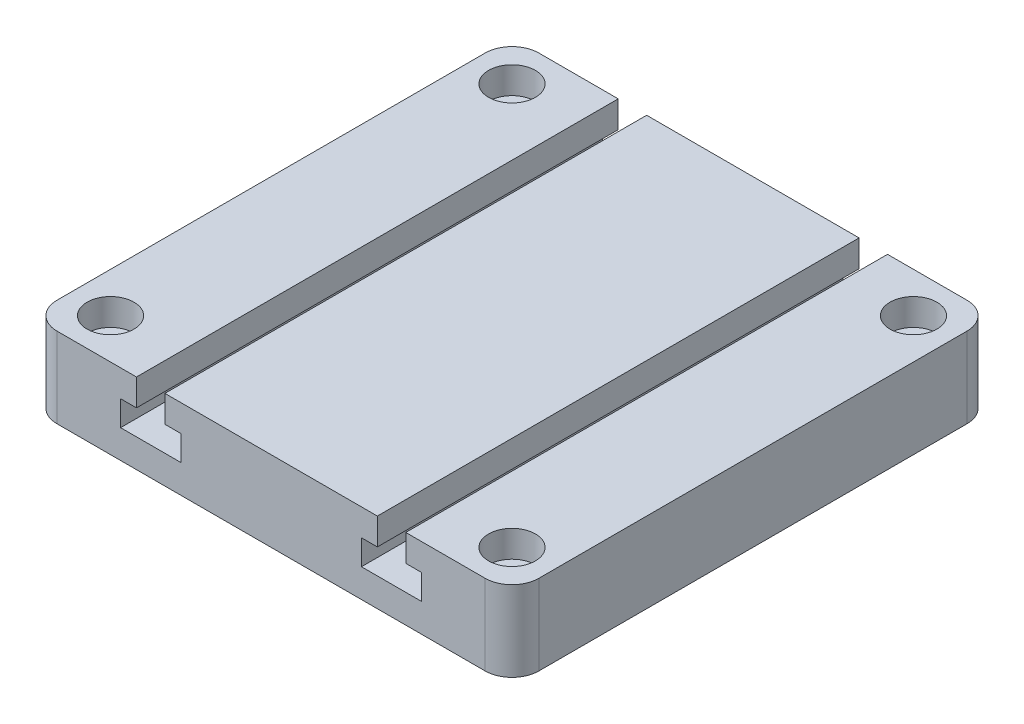
SolidWorks part; units mm, degrees
material "Delrin 2700 NC010, Low Viscosity Acetal Copolymer (SS)"
ref_plane "Front" through (0, 0, 0) normal (0, 0, 1) x (1, 0, 0)
ref_plane "Top" through (0, 0, 0) normal (0, 1, 0) x (1, 0, 0)
ref_plane "Right" through (0, 0, 0) normal (1, 0, 0) x (0, 0, -1)
sketch "Sketch1" plane through (0, 0, 0) normal (0, 1, 0) x (1, 0, 0)
  line L1 (-57.15, 57.15) -> (57.15, 57.15)
  line L2 (-57.15, 57.15) -> (-57.15, -57.15)
  line L3 (-57.15, -57.15) -> (57.15, -57.15)
  line L4 (57.15, 57.15) -> (57.15, -57.15)
  line L5 (-57.15, 57.15) -> (57.15, -57.15) construction
  line L6 (-57.15, -57.15) -> (57.15, 57.15) construction
  point P0 (0, 0)
  dimension "D1" = 114.3
  dimension "D2" = 114.3
extrude "Boss-Extrude1" add sketch "Sketch1" along normal blind 19.05
hole_wizard "CBORE for 1/4 Socket Head Cap Screw1" positions "Sketch2" profile "Sketch3" counterbore size "1/4" standard "ANSI Inch" end condition through all
sketch "Sketch2" plane through (0, 19.05, 0) normal (0, 1, 0) x (1, 0, 0)
  line L1 (-47.625, 47.625) -> (47.625, 47.625) construction
  line L2 (-47.625, 47.625) -> (-47.625, -47.625) construction
  line L3 (-47.625, -47.625) -> (47.625, -47.625) construction
  line L4 (47.625, 47.625) -> (47.625, -47.625) construction
  line L5 (-47.625, 47.625) -> (47.625, -47.625) construction
  line L6 (-47.625, -47.625) -> (47.625, 47.625) construction
  point P0 (-47.625, 47.625)
  point P2 (47.625, 47.625)
  point P4 (47.625, -47.625)
  point P6 (-47.625, -47.625)
  point P108 (0, 0)
  dimension "D1" = 95.25
  dimension "D2" = 95.25
sketch "Sketch3" plane through (-47.625, 19.05, -47.625) normal (1, 0, 0) x (0, 0, 1)
  line L0 (0, 0) -> (0, 19.05)
  line L1 (0, 19.05) -> (3.2639, 19.05)
  line L3 (3.2639, 19.05) -> (3.2639, 6.35)
  line L4 (3.2639, 6.35) -> (5.5562, 6.35)
  line L5 (5.5562, 6.35) -> (5.5562, 0)
  line L7 (5.5562, 0) -> (0, 0)
  line L11 (0, -6.35) -> (0, 107.95) construction
  dimension "Thru Hole Dia." = 6.5278
  dimension "Thru Hole Depth" = 19.05
  dimension "C'Bore Dia." = 11.1125
  dimension "C'Bore Depth" = 6.35
sketch "Sketch4" plane through (0, 0, 57.15) normal (0, 0, 1) x (1, 0, 0)
  line L0 (-31.9484, 19.05) -> (-31.9484, 12.7)
  line L1 (-57.15, 19.05) -> (57.15, 19.05) construction
  line L2 (-31.9484, 12.7) -> (-35.7188, 12.7)
  line L3 (-35.7188, 12.7) -> (-35.7188, 6.7469)
  line L4 (-35.7188, 6.7469) -> (-21.4312, 6.7469)
  line L5 (-21.4312, 6.7469) -> (-21.4312, 12.7)
  line L6 (-21.4312, 12.7) -> (-25.2016, 12.7)
  line L7 (-25.2016, 12.7) -> (-25.2016, 19.05)
  line L8 (0, 0) -> (0, 19.05) construction
  line L9 (-28.575, 6.7469) -> (-28.575, 19.05) construction
  line L10 (28.575, 6.7469) -> (28.575, 19.05) construction
  line L11 (25.2016, 12.7) -> (25.2016, 19.05)
  line L12 (21.4312, 12.7) -> (25.2016, 12.7)
  line L13 (21.4312, 6.7469) -> (21.4312, 12.7)
  line L14 (35.7188, 6.7469) -> (21.4312, 6.7469)
  line L15 (35.7188, 12.7) -> (35.7188, 6.7469)
  line L16 (31.9484, 12.7) -> (35.7188, 12.7)
  line L17 (31.9484, 19.05) -> (31.9484, 12.7)
  line L18 (-31.9484, 19.05) -> (-25.2016, 19.05)
  line L19 (25.2016, 19.05) -> (31.9484, 19.05)
  line L20 (-57.15, 0) -> (57.15, 0) construction
  dimension "D1" = 14.2875
  dimension "D2" = 6.7469
  dimension "D3" = 6.35
  dimension "D4" = 57.15
  dimension "D5" = 5.9531
  dimension "D6" = 6.7469
extrude "T-SLOT CUT WITH MCMASTER 8789A16 BIT" cut sketch "Sketch4" against normal through all
fillet "Fillet1" radius 6.35 4 edges at (-57.15, 9.525, 57.15) (57.15, 9.525, 57.15) (57.15, 9.525, -57.15) (-57.15, 9.525, -57.15)
